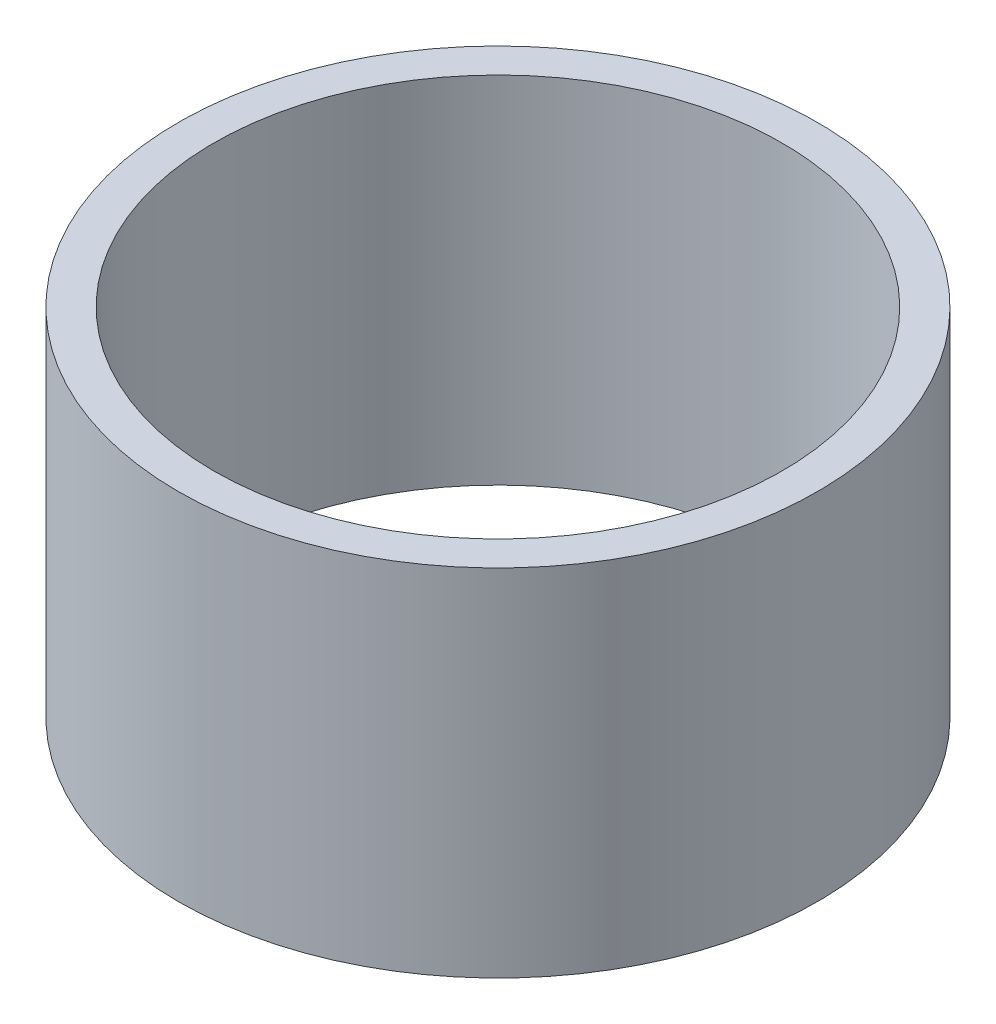
SolidWorks part; units mm, degrees
material "Epoxy, Unfilled"
ref_plane "Front Plane" through (0, 0, 0) normal (0, 0, 1) x (1, 0, 0)
ref_plane "Top Plane" through (0, 0, 0) normal (0, 1, 0) x (1, 0, 0)
ref_plane "Right Plane" through (0, 0, 0) normal (1, 0, 0) x (0, 0, -1)
sketch "Sketch1" plane through (0, 0, 0) normal (0, 1, 0) x (1, 0, 0)
  circle A0 centre (0, 0) radius 57.15
  circle A1 centre (0, 0) radius 57.15
  circle A2 centre (0, 0) radius 50.8
extrude "Boss-Extrude1" add sketch "Sketch1" along normal blind 63.5 contours A0 A2 region at (-55.5336, 0, 0)
